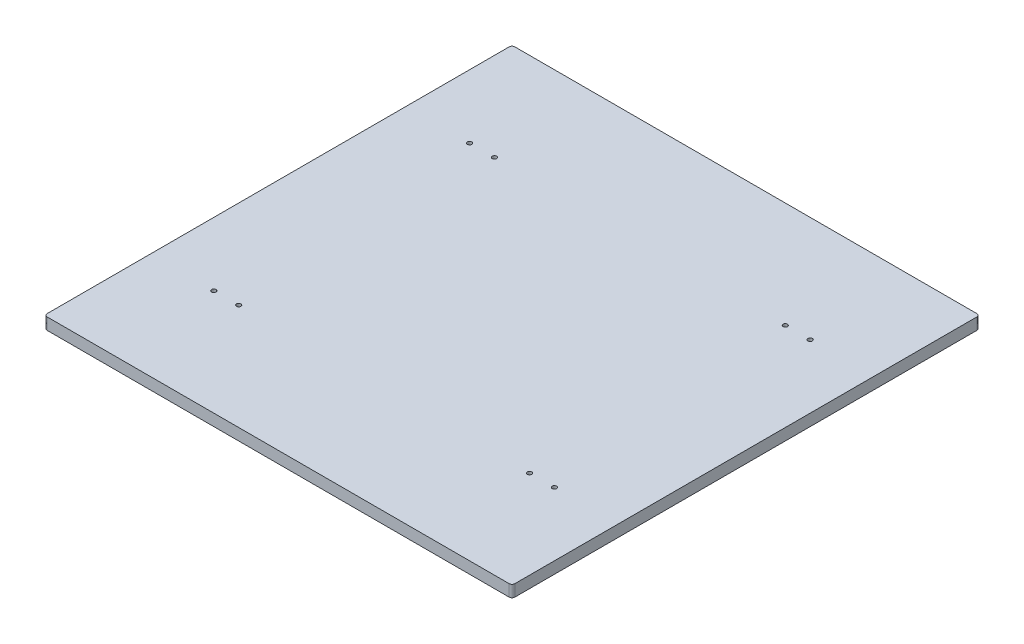
SolidWorks part; units mm, degrees
material "PMMA"
ref_plane "前视基准面" through (0, 0, 0) normal (0, 0, 1) x (1, 0, 0)
ref_plane "上视基准面" through (0, 0, 0) normal (0, 1, 0) x (1, 0, 0)
ref_plane "右视基准面" through (0, 0, 0) normal (1, 0, 0) x (0, 0, -1)
sketch "草图1" plane through (0, 0, 0) normal (0, 1, 0) x (1, 0, 0)
  line L1 (-158, -160) -> (158, -160)
  line L2 (-160, -158) -> (-160, 158)
  line L3 (-158, 160) -> (158, 160)
  line L4 (160, -158) -> (160, 158)
  line L5 (-160, -160) -> (160, 160) construction
  line L6 (-160, 160) -> (160, -160) construction
  arc A0 (160, -158) -> (158, -160) centre (158, -158) cw
  arc A1 (-158, -160) -> (-160, -158) centre (-158, -158) cw
  arc A2 (160, 158) -> (158, 160) centre (158, 158) ccw
  arc A3 (-158, 160) -> (-160, 158) centre (-158, 158) ccw
  point P0 (0, 0)
  dimension "D3" = 2
  dimension "D1" = 320
  dimension "D2" = 320
extrude "凸台-拉伸1" add sketch "草图1" against normal blind 8
sketch "Sketch2" plane through (0, -8, 0) normal (0, -1, 0) x (1, 0, 0)
  line L0 (0, -160) -> (0, 165.2098) construction
  line L1 (158, -160) -> (-158, -160) construction
  line L2 (-160, 0) -> (160, 0) construction
  line L3 (-160, -158) -> (-160, 158) construction
  line L4 (160, 158) -> (160, -158) construction
  line L5 (-116.5, -87.5) -> (-116.5, 87.5) construction
  line L6 (-116.5, 87.5) -> (-99.5, 87.5) construction
  line L7 (-99.5, 87.5) -> (-99.5, -87.5) construction
  line L8 (-116.5, -87.5) -> (-99.5, -87.5) construction
  line L9 (116.5, -87.5) -> (99.5, -87.5) construction
  line L10 (99.5, 87.5) -> (99.5, -87.5) construction
  line L11 (116.5, 87.5) -> (99.5, 87.5) construction
  line L12 (116.5, -87.5) -> (116.5, 87.5) construction
  circle A0 centre (-116.5, 87.5) radius 1.5
  circle A1 centre (-99.5, 87.5) radius 1.5
  circle A2 centre (-116.5, -87.5) radius 1.5
  circle A3 centre (-99.5, -87.5) radius 1.5
  circle A4 centre (99.5, -87.5) radius 1.5
  circle A5 centre (116.5, -87.5) radius 1.5
  circle A6 centre (99.5, 87.5) radius 1.5
  circle A7 centre (116.5, 87.5) radius 1.5
  point P16 (-99.5, 0)
  point P17 (-116.5, 0)
  point P29 (116.5, 0)
  point P30 (99.5, 0)
  dimension "D4" = 3
  dimension "D5" = 3
  dimension "D6" = 3
  dimension "D7" = 3
  dimension "D1" = 87.5
  dimension "D2" = 17
  dimension "D3" = 116.5
extrude "Cut-Extrude1" cut sketch "Sketch2" against normal through all
